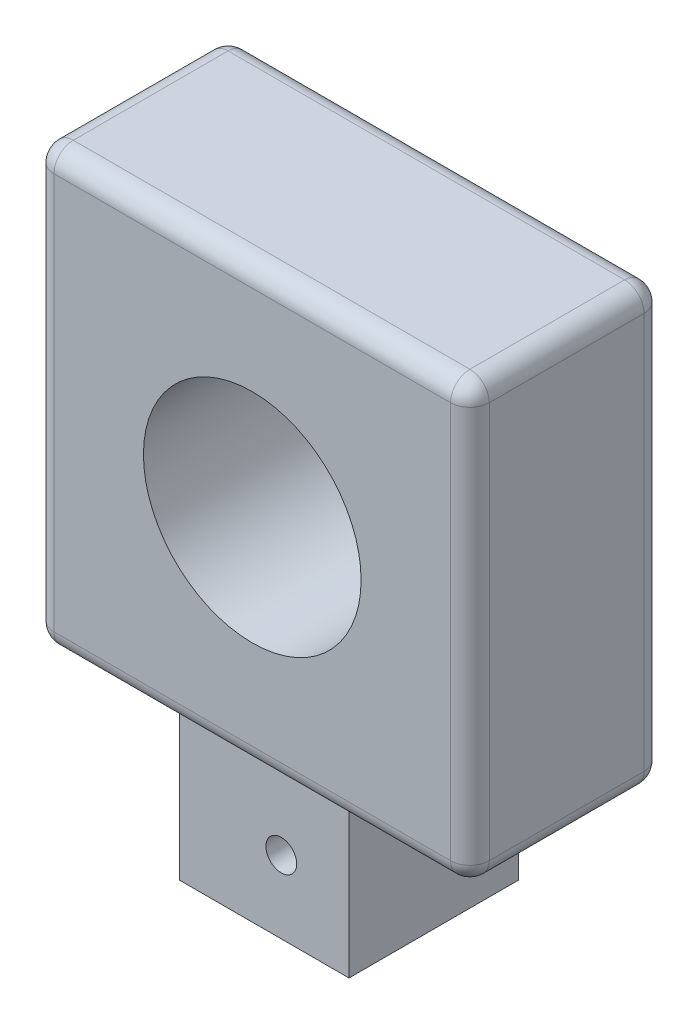
SolidWorks part; units mm, degrees
ref_plane "Front Plane" through (0, 0, 0) normal (0, 0, 1) x (1, 0, 0)
ref_plane "Top Plane" through (0, 0, 0) normal (0, 1, 0) x (1, 0, 0)
ref_plane "Right Plane" through (0, 0, 0) normal (1, 0, 0) x (0, 0, -1)
sketch "Sketch1" plane through (0, 0, 0) normal (0, 1, 0) x (1, 0, 0)
  line L1 (-11.1125, -11.1125) -> (11.1125, -11.1125)
  line L2 (-11.1125, -11.1125) -> (-11.1125, 11.1125)
  line L3 (-11.1125, 11.1125) -> (11.1125, 11.1125)
  line L4 (11.1125, -11.1125) -> (11.1125, 11.1125)
  line L5 (-11.1125, -11.1125) -> (11.1125, 11.1125) construction
  line L6 (-11.1125, 11.1125) -> (11.1125, -11.1125) construction
  point P0 (0, 0)
  dimension "D2" = 22.225
extrude "Boss-Extrude1" add sketch "Sketch1" along normal blind 12.7 and the other way blind 6.35
sketch "Sketch2" plane through (0, 12.7, 0) normal (0, 1, 0) x (1, 0, 0)
  line L1 (-28.575, -12.7) -> (28.575, -12.7)
  line L2 (-28.575, -12.7) -> (-28.575, 12.7)
  line L3 (-28.575, 12.7) -> (28.575, 12.7)
  line L4 (28.575, -12.7) -> (28.575, 12.7)
  line L5 (-28.575, -12.7) -> (28.575, 12.7) construction
  line L6 (-28.575, 12.7) -> (28.575, -12.7) construction
  point P0 (0, 0)
  dimension "D1" = 57.15
  dimension "D2" = 25.4
extrude "Boss-Extrude2" add sketch "Sketch2" along normal blind 57.15
sketch "Sketch3" plane through (0, 0, 12.7) normal (0, 0, 1) x (1, 0, 0)
  line L0 (-28.575, 69.85) -> (28.575, 69.85) construction
  line L1 (28.575, 69.85) -> (28.575, 12.7) construction
  circle A0 centre (0, 41.275) radius 14.2875
  dimension "D1" = 28.575
  dimension "D2" = 28.575
  dimension "D3" = 28.575
extrude "Cut-Extrude1" cut sketch "Sketch3" against normal through all
fillet "Fillet1" radius 2.54 12 edges at (28.575, 69.85, 0) (28.575, 12.7, 0) (-28.575, 69.85, 0) (-28.575, 12.7, 0) (28.575, 41.275, -12.7) (0, 69.85, -12.7) (-28.575, 41.275, -12.7) (0, 12.7, -12.7) (-28.575, 41.275, 12.7) (0, 69.85, 12.7) (28.575, 41.275, 12.7) (0, 12.7, 12.7)
sketch "Sketch4" plane through (0, 0, -11.1125) normal (0, 0, -1) x (-1, 0, 0)
  line L0 (-11.1125, -6.35) -> (11.1125, -6.35) construction
  line L1 (-11.1125, -6.35) -> (-11.1125, 12.8854) construction
  circle A0 centre (-2.2225, 3.175) radius 2.0193
  dimension "D1" = 4.0386
  dimension "D2" = 9.525
  dimension "D3" = 8.89
extrude "Cut-Extrude2" cut sketch "Sketch4" against normal through all
